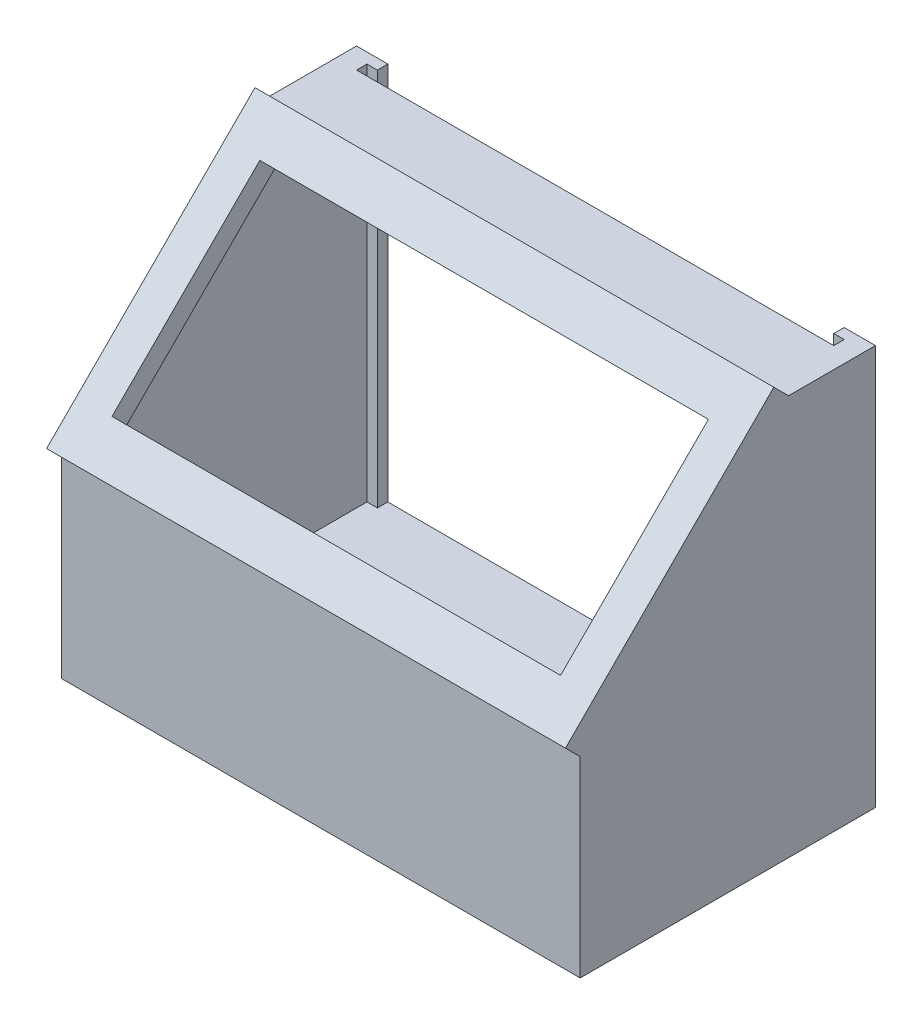
SolidWorks part; units mm, degrees
ref_plane "Front Plane" through (0, 0, 0) normal (0, 0, 1) x (1, 0, 0)
ref_plane "Top Plane" through (0, 0, 0) normal (0, 1, 0) x (1, 0, 0)
ref_plane "Right Plane" through (0, 0, 0) normal (1, 0, 0) x (0, 0, -1)
sketch "Sketch1" plane through (0, 0, 0) normal (0, 1, 0) x (1, 0, 0)
  line L1 (-124.5019, 65.8387) -> (124.5019, 65.8387)
  line L2 (-124.5019, 65.8387) -> (-124.5019, -65.8387)
  line L3 (-124.5019, -65.8387) -> (124.5019, -65.8387)
  line L4 (124.5019, 65.8387) -> (124.5019, -65.8387)
  line L5 (-124.5019, 65.8387) -> (124.5019, -65.8387) construction
  line L6 (-124.5019, -65.8387) -> (124.5019, 65.8387) construction
  point P0 (0, 0)
extrude "Boss-Extrude1" add sketch "Sketch1" along normal blind 192
chamfer "Chamfer1" distance 100 angle 45 1 edges at (0, 192, 65.8387)
sketch "Sketch2" plane through (0, 78.9194, 78.9194) normal (0, 0.7071, 0.7071) x (1, 0, 0)
  line L0 (0, 0) -> (0, 159.9202) construction
  line L1 (-124.5019, 89.2095) -> (124.5019, 89.2095) construction
  line L3 (-107.6303, 139.3742) -> (107.6303, 139.3742)
  line L4 (-124.5019, 159.9202) -> (-124.5019, 18.4988)
  line L5 (-124.5019, 18.4988) -> (124.5019, 18.4988)
  line L6 (124.5019, 18.4988) -> (124.5019, 159.9202)
  line L7 (124.5019, 159.9202) -> (-124.5019, 159.9202)
  line L8 (-124.5019, 159.9202) -> (-124.5019, 18.4988)
  line L9 (-124.5019, 18.4988) -> (124.5019, 18.4988)
  line L10 (124.5019, 18.4988) -> (124.5019, 159.9202)
  line L11 (124.5019, 159.9202) -> (-124.5019, 159.9202)
  line L12 (-107.6303, 139.3742) -> (-107.6303, 39.0448)
  line L13 (-107.6303, 39.0448) -> (107.6303, 39.0448)
  line L14 (107.6303, 139.3742) -> (107.6303, 39.0448)
  line L15 (-107.6303, 139.3742) -> (107.6303, 39.0448) construction
  line L16 (-107.6303, 39.0448) -> (107.6303, 139.3742) construction
  point P9 (0, 89.2095)
  dimension "D2" = 215.2606
  dimension "D3" = 100.3293
  dimension "D1" = 0
extrude "Boss-Extrude2" add sketch "Sketch2" along normal blind 10
shell "Shell1" thickness 10 removed face at (0, 142, 15.8387) removed face at (0, 96, -65.8387)
sketch "Sketch3" plane through (0, 0, -65.8387) normal (0, 0, -1) x (-1, 0, 0)
  line L0 (-114.5019, 182) -> (-114.5019, 192)
  line L1 (114.5019, 182) -> (114.5019, 192)
  line L2 (114.5019, 182) -> (114.5019, 10) construction
  line L4 (-124.5019, 0) -> (124.5019, 0)
  line L5 (124.5019, 0) -> (124.5019, 192)
  line L6 (124.5019, 192) -> (-124.5019, 192)
  line L7 (-124.5019, 192) -> (-124.5019, 0)
  line L8 (-124.5019, 0) -> (124.5019, 0)
  line L9 (124.5019, 0) -> (124.5019, 192)
  line L10 (124.5019, 192) -> (-124.5019, 192)
  line L11 (-124.5019, 192) -> (-124.5019, 0)
  line M5 (-124.5019, 0) -> (124.5019, 0)
  line M6 (124.5019, 0) -> (124.5019, 192)
  line M7 (124.5019, 192) -> (-124.5019, 192)
  line M8 (-124.5019, 192) -> (-124.5019, 0)
  line M9 (114.5019, 10) -> (-114.5019, 10)
  line M10 (-114.5019, 10) -> (-114.5019, 182)
  line M12 (114.5019, 182) -> (114.5019, 10)
  dimension "D1" = 0
extrude "Boss-Extrude3" add sketch "Sketch3" along normal blind 5 contours L1 L0 M12 M9 M10 M7 M8 M5 M6 region at (117.6462, 96, -65.8387)
sketch "Sketch4" plane through (0, 0, -70.8387) normal (0, 0, -1) x (-1, 0, 0)
  line L0 (-114.5019, 192) -> (-109.5019, 192)
  line L1 (-114.5019, 192) -> (114.5019, 192) construction
  line L2 (-109.5019, 192) -> (-109.5019, 10)
  line L3 (-109.5019, 10) -> (109.5019, 10)
  line L4 (109.5019, 10) -> (109.5019, 192)
  line L5 (109.5019, 192) -> (114.5019, 192)
  line L8 (114.5019, 192) -> (114.5019, 10)
  line L9 (114.5019, 10) -> (-114.5019, 10)
  line L10 (-114.5019, 10) -> (-114.5019, 192)
  line L11 (-114.5019, 192) -> (-124.5019, 192)
  line L12 (-124.5019, 192) -> (-124.5019, 0)
  line L13 (-124.5019, 0) -> (124.5019, 0)
  line L14 (124.5019, 0) -> (124.5019, 192)
  line L15 (124.5019, 192) -> (114.5019, 192)
  line L16 (114.5019, 192) -> (114.5019, 10)
  line L17 (114.5019, 10) -> (-114.5019, 10)
  line L18 (-114.5019, 10) -> (-114.5019, 192)
  line L19 (-114.5019, 192) -> (-124.5019, 192)
  line L20 (-124.5019, 192) -> (-124.5019, 0)
  line L21 (-124.5019, 0) -> (124.5019, 0)
  line L22 (124.5019, 0) -> (124.5019, 192)
  line L23 (124.5019, 192) -> (114.5019, 192)
  line M12 (114.5019, 192) -> (114.5019, 10)
  line M13 (114.5019, 10) -> (-114.5019, 10)
  line M14 (-114.5019, 10) -> (-114.5019, 192)
  line M15 (-114.5019, 192) -> (-124.5019, 192)
  line M16 (-124.5019, 192) -> (-124.5019, 0)
  line M17 (-124.5019, 0) -> (124.5019, 0)
  line M18 (124.5019, 0) -> (124.5019, 192)
  line M19 (124.5019, 192) -> (114.5019, 192)
  dimension "D2" = 5
  dimension "D3" = 0
  dimension "D4" = 5
  dimension "D1" = 0
extrude "Boss-Extrude4" add sketch "Sketch4" along normal blind 5 contours M19 M12 M13 M14 M15 M16 M17 M18 | L5 L4 M13 M12 | L2 L0 M14 M13 region at (112.0019, 101, -70.8387) region at (117.6462, 101, -70.8387) region at (-112.0019, 101, -70.8387)
